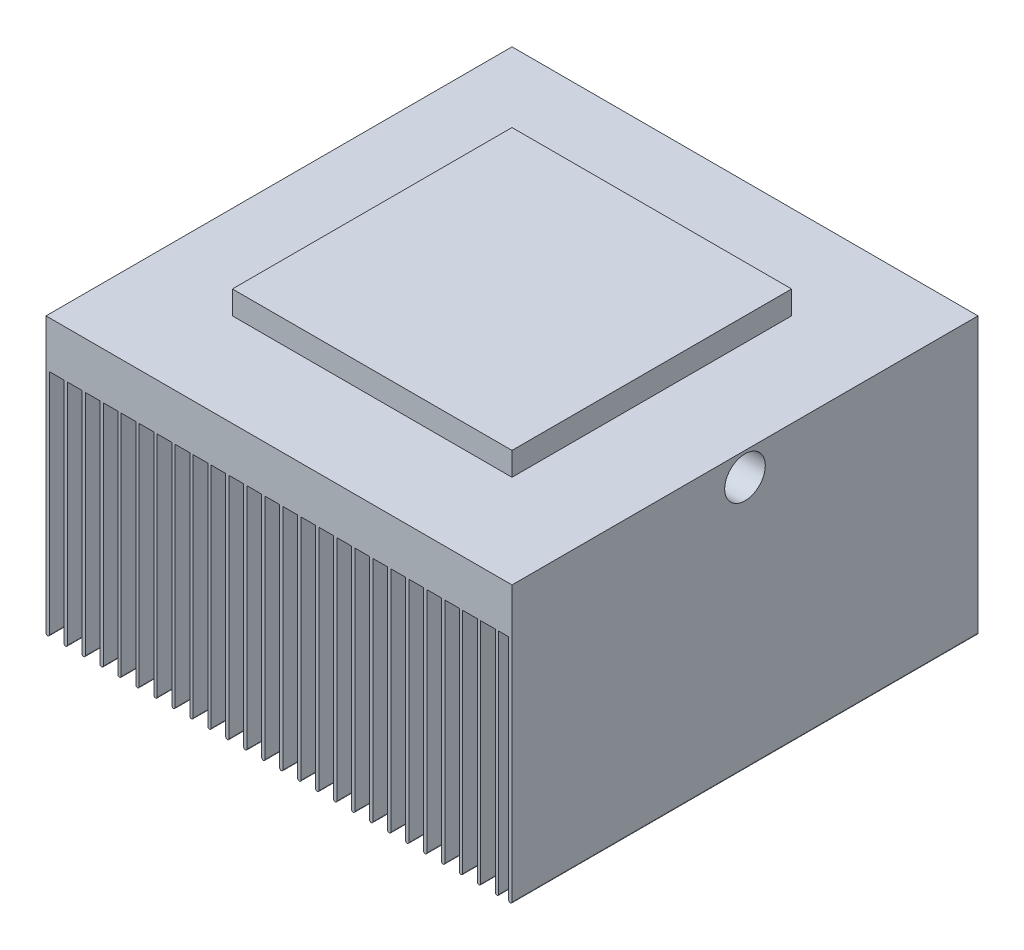
SolidWorks part; units mm, degrees
ref_plane "前视基准面" through (0, 0, 0) normal (0, 0, 1) x (1, 0, 0)
ref_plane "上视基准面" through (0, 0, 0) normal (0, 1, 0) x (1, 0, 0)
ref_plane "右视基准面" through (0, 0, 0) normal (1, 0, 0) x (0, 0, -1)
sketch "草图1" plane through (0, 0, 0) normal (0, 1, 0) x (1, 0, 0)
  line L1 (-35, -35) -> (35, -35)
  line L2 (-35, -35) -> (-35, 35)
  line L3 (-35, 35) -> (35, 35)
  line L4 (35, -35) -> (35, 35)
  line L5 (-35, -35) -> (35, 35) construction
  line L6 (-35, 35) -> (35, -35) construction
  point P0 (0, 0)
  dimension "D1" = 70
  dimension "D2" = 70
extrude "凸台-拉伸1" add sketch "草图1" along normal blind 41.5
sketch "草图2" plane through (0, 41.5, 0) normal (0, 1, 0) x (1, 0, 0)
  line L1 (-21, -21) -> (21, -21)
  line L2 (-21, -21) -> (-21, 21)
  line L3 (-21, 21) -> (21, 21)
  line L4 (21, -21) -> (21, 21)
  line L5 (-21, -21) -> (21, 21) construction
  line L6 (-21, 21) -> (21, -21) construction
  point P0 (0, 0)
  dimension "D1" = 42
extrude "凸台-拉伸2" add sketch "草图2" along normal blind 3.5
sketch "草图3" plane through (0, 0, 35) normal (0, 0, 1) x (1, 0, 0)
  line L0 (-35, 34.5) -> (35, 34.5) construction
  line L1 (-35, 41.5) -> (-35, 0) construction
  line L2 (35, 41.5) -> (35, 0) construction
  line L3 (-35, 41.5) -> (35, 41.5) construction
  line L4 (-35, 34.5) -> (-35, 0.25)
  line L5 (-34.5, 34.5) -> (-32.3, 34.5)
  line L7 (-34.5, 0.25) -> (-34.5, 34.5)
  line L8 (-35, 0) -> (35, 0) construction
  line L9 (-31.8, 34.5) -> (-29.6, 34.5)
  line L10 (-31.8, 0.25) -> (-31.8, 34.5)
  line L11 (-32.3, 34.5) -> (-32.3, 0.25)
  line L12 (-29.1, 34.5) -> (-26.9, 34.5)
  line L13 (-29.1, 0.25) -> (-29.1, 34.5)
  line L14 (-29.6, 34.5) -> (-29.6, 0.25)
  line L15 (-26.4, 34.5) -> (-24.2, 34.5)
  line L16 (-26.4, 0.25) -> (-26.4, 34.5)
  line L17 (-26.9, 34.5) -> (-26.9, 0.25)
  line L18 (-23.7, 34.5) -> (-21.5, 34.5)
  line L19 (-23.7, 0.25) -> (-23.7, 34.5)
  line L20 (-24.2, 34.5) -> (-24.2, 0.25)
  line L21 (-21, 34.5) -> (-18.8, 34.5)
  line L22 (-21, 0.25) -> (-21, 34.5)
  line L23 (-21.5, 34.5) -> (-21.5, 0.25)
  line L24 (-18.3, 34.5) -> (-16.1, 34.5)
  line L25 (-18.3, 0.25) -> (-18.3, 34.5)
  line L26 (-18.8, 34.5) -> (-18.8, 0.25)
  line L27 (-15.6, 34.5) -> (-13.4, 34.5)
  line L28 (-15.6, 0.25) -> (-15.6, 34.5)
  line L29 (-16.1, 34.5) -> (-16.1, 0.25)
  line L30 (-12.9, 34.5) -> (-10.7, 34.5)
  line L31 (-12.9, 0.25) -> (-12.9, 34.5)
  line L32 (-13.4, 34.5) -> (-13.4, 0.25)
  line L33 (-10.2, 34.5) -> (-8, 34.5)
  line L34 (-10.2, 0.25) -> (-10.2, 34.5)
  line L35 (-10.7, 34.5) -> (-10.7, 0.25)
  line L36 (-7.5, 34.5) -> (-5.3, 34.5)
  line L37 (-7.5, 0.25) -> (-7.5, 34.5)
  line L38 (-8, 34.5) -> (-8, 0.25)
  line L39 (-4.8, 34.5) -> (-2.6, 34.5)
  line L40 (-4.8, 0.25) -> (-4.8, 34.5)
  line L41 (-5.3, 34.5) -> (-5.3, 0.25)
  line L42 (-2.1, 34.5) -> (0.1, 34.5)
  line L43 (-2.1, 0.25) -> (-2.1, 34.5)
  line L44 (-2.6, 34.5) -> (-2.6, 0.25)
  line L45 (0.6, 34.5) -> (2.8, 34.5)
  line L46 (0.6, 0.25) -> (0.6, 34.5)
  line L47 (0.1, 34.5) -> (0.1, 0.25)
  line L48 (3.3, 34.5) -> (5.5, 34.5)
  line L49 (3.3, 0.25) -> (3.3, 34.5)
  line L50 (2.8, 34.5) -> (2.8, 0.25)
  line L51 (6, 34.5) -> (8.2, 34.5)
  line L52 (6, 0.25) -> (6, 34.5)
  line L53 (5.5, 34.5) -> (5.5, 0.25)
  line L54 (8.7, 34.5) -> (10.9, 34.5)
  line L55 (8.7, 0.25) -> (8.7, 34.5)
  line L56 (8.2, 34.5) -> (8.2, 0.25)
  line L57 (11.4, 34.5) -> (13.6, 34.5)
  line L58 (11.4, 0.25) -> (11.4, 34.5)
  line L59 (10.9, 34.5) -> (10.9, 0.25)
  line L60 (14.1, 34.5) -> (16.3, 34.5)
  line L61 (14.1, 0.25) -> (14.1, 34.5)
  line L62 (13.6, 34.5) -> (13.6, 0.25)
  line L63 (16.8, 34.5) -> (19, 34.5)
  line L64 (16.8, 0.25) -> (16.8, 34.5)
  line L65 (16.3, 34.5) -> (16.3, 0.25)
  line L66 (19.5, 34.5) -> (21.7, 34.5)
  line L67 (19.5, 0.25) -> (19.5, 34.5)
  line L68 (19, 34.5) -> (19, 0.25)
  line L69 (22.2, 34.5) -> (24.4, 34.5)
  line L70 (22.2, 0.25) -> (22.2, 34.5)
  line L71 (21.7, 34.5) -> (21.7, 0.25)
  line L72 (24.9, 34.5) -> (27.1, 34.5)
  line L73 (24.9, 0.25) -> (24.9, 34.5)
  line L74 (24.4, 34.5) -> (24.4, 0.25)
  line L75 (27.6, 34.5) -> (29.8, 34.5)
  line L76 (27.6, 0.25) -> (27.6, 34.5)
  line L77 (27.1, 34.5) -> (27.1, 0.25)
  line L78 (30.3, 34.5) -> (32.5, 34.5)
  line L79 (30.3, 0.25) -> (30.3, 34.5)
  line L80 (29.8, 34.5) -> (29.8, 0.25)
  line L81 (35, 0.25) -> (35, 34.5)
  line L82 (33, 0.25) -> (33, 34.5)
  line L83 (32.5, 34.5) -> (32.5, 0.25)
  line L84 (33, 34.5) -> (35.2, 34.5) [skipped]
  line L85 (34.5, 34.5) -> (34.5, 0.25)
  line L86 (33, 34.5) -> (34.5, 34.5)
  line L87 (-35, 0) -> (35, 0)
  arc A0 (-35, 0.25) -> (-34.5, 0.25) centre (-34.75, 0.25) ccw
  arc A1 (-32.3, 0.25) -> (-31.8, 0.25) centre (-32.05, 0.25) ccw
  arc A2 (-29.6, 0.25) -> (-29.1, 0.25) centre (-29.35, 0.25) ccw
  arc A3 (-26.9, 0.25) -> (-26.4, 0.25) centre (-26.65, 0.25) ccw
  arc A4 (-24.2, 0.25) -> (-23.7, 0.25) centre (-23.95, 0.25) ccw
  arc A5 (-21.5, 0.25) -> (-21, 0.25) centre (-21.25, 0.25) ccw
  arc A6 (-18.8, 0.25) -> (-18.3, 0.25) centre (-18.55, 0.25) ccw
  arc A7 (-16.1, 0.25) -> (-15.6, 0.25) centre (-15.85, 0.25) ccw
  arc A8 (-13.4, 0.25) -> (-12.9, 0.25) centre (-13.15, 0.25) ccw
  arc A9 (-10.7, 0.25) -> (-10.2, 0.25) centre (-10.45, 0.25) ccw
  arc A10 (-8, 0.25) -> (-7.5, 0.25) centre (-7.75, 0.25) ccw
  arc A11 (-5.3, 0.25) -> (-4.8, 0.25) centre (-5.05, 0.25) ccw
  arc A12 (-2.6, 0.25) -> (-2.1, 0.25) centre (-2.35, 0.25) ccw
  arc A13 (0.1, 0.25) -> (0.6, 0.25) centre (0.35, 0.25) ccw
  arc A14 (2.8, 0.25) -> (3.3, 0.25) centre (3.05, 0.25) ccw
  arc A15 (5.5, 0.25) -> (6, 0.25) centre (5.75, 0.25) ccw
  arc A16 (8.2, 0.25) -> (8.7, 0.25) centre (8.45, 0.25) ccw
  arc A17 (10.9, 0.25) -> (11.4, 0.25) centre (11.15, 0.25) ccw
  arc A18 (13.6, 0.25) -> (14.1, 0.25) centre (13.85, 0.25) ccw
  arc A19 (16.3, 0.25) -> (16.8, 0.25) centre (16.55, 0.25) ccw
  arc A20 (19, 0.25) -> (19.5, 0.25) centre (19.25, 0.25) ccw
  arc A21 (21.7, 0.25) -> (22.2, 0.25) centre (21.95, 0.25) ccw
  arc A22 (24.4, 0.25) -> (24.9, 0.25) centre (24.65, 0.25) ccw
  arc A23 (27.1, 0.25) -> (27.6, 0.25) centre (27.35, 0.25) ccw
  arc A24 (29.8, 0.25) -> (30.3, 0.25) centre (30.05, 0.25) ccw
  arc A25 (32.5, 0.25) -> (33, 0.25) centre (32.75, 0.25) ccw
  arc A26 (34.5, 0.25) -> (35, 0.25) centre (34.75, 0.25) ccw
  line M108 (-35, 0) -> (35, 0)
  dimension "D1" = 7
  dimension "D2" = 0.5
  dimension "D3" = 2.2
  dimension "D5" = 0.5
  dimension "D4" = 26
extrude "切除-拉伸1" cut sketch "草图3" against normal through all contours A1 L11 L5 L7 A0 L87 | A2 L14 L9 L10 A1 M108 | A3 L17 L12 L13 A2 L87 | A4 L20 L15 L16 A3 M108 | A5 L23 L18 L19 A4 L87 | A6 L26 L21 L22 A5 M108 | A7 L29 L24 L25 A6 L87 | A8 L32 L27 L28 A7 M108 | A9 L35 L30 L31 A8 L87 | A10 L38 L33 L34 A9 M108 | A11 L41 L36 L37 A10 L87 | A12 L44 L39 L40 A11 M108 | A13 L47 L42 L43 A12 L87 | A14 L50 L45 L46 A13 M108 | A15 L53 L48 L49 A14 L87 | A16 L56 L51 L52 A15 M108 | A17 L59 L54 L55 A16 L87 | A18 L62 L57 L58 A17 M108 | A19 L65 L60 L61 A18 L87 | A20 L68 L63 L64 A19 M108 | A21 L71 L66 L67 A20 L87 | A22 L74 L69 L70 A21 M108 | A23 L77 L72 L73 A22 L87 | A24 L80 L75 L76 A23 M108 | A25 L83 L78 L79 A24 L87 | A26 L85 L86 L82 A25 M108 region at (33.75, 17.2411, 35) region at (31.4, 17.2439, 35) region at (28.7, 17.2439, 35) region at (26, 17.2439, 35) region at (23.3, 17.2439, 35) region at (20.6, 17.2439, 35) region at (17.9, 17.2439, 35) region at (15.2, 17.2439, 35) region at (12.5, 17.2439, 35) region at (9.8, 17.2439, 35) region at (7.1, 17.2439, 35) region at (4.4, 17.2439, 35) region at (1.7, 17.2439, 35) region at (-1, 17.2439, 35) region at (-3.7, 17.2439, 35) region at (-6.4, 17.2439, 35) region at (-9.1, 17.2439, 35) region at (-11.8, 17.2439, 35) region at (-14.5, 17.2439, 35) region at (-17.2, 17.2439, 35) region at (-19.9, 17.2439, 35) region at (-22.6, 17.2439, 35) region at (-25.3, 17.2439, 35) region at (-28, 17.2439, 35) region at (-30.7, 17.2439, 35) region at (-33.4, 17.2439, 35)
fillet "圆角1" radius 0.25 1 edges at (-35, 0, 0)
fillet "圆角2" radius 0.25 1 edges at (35, 0, 0)
sketch "草图6" plane through (35, 0, 0) normal (1, 0, 0) x (0, 0, -1)
  line L0 (-35, 41.5) -> (35, 41.5) construction
  circle A0 centre (0, 38) radius 3.05
  dimension "D1" = 6.1
  dimension "D2" = 3.5
extrude "切除-拉伸2" cut sketch "草图6" against normal blind 52
